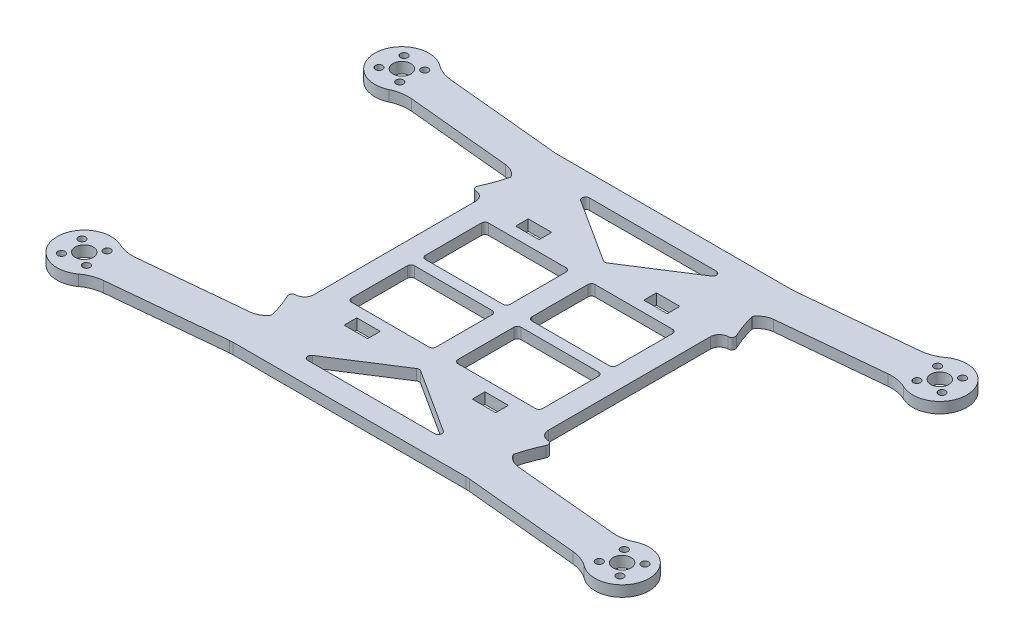
SolidWorks part; units mm, degrees
material "Custom PLA"
ref_plane "Front Plane" through (0, 0, 0) normal (0, 0, 1) x (1, 0, 0)
ref_plane "Top Plane" through (0, 0, 0) normal (0, 1, 0) x (1, 0, 0)
ref_plane "Right Plane" through (0, 0, 0) normal (1, 0, 0) x (0, 0, -1)
sketch "Sketch1" plane through (0, 0, 0) normal (0, 1, 0) x (1, 0, 0)
  line L0 (-101.3207, 0) -> (4964.7124, 0) construction
  line L1 (0, -101.3207) -> (0, 4964.7124) construction
  line L4 (33.2085, 45.046) -> (65.0466, 48.1117)
  line L5 (37.1258, 35.377) -> (66.0089, 38.1581)
  line L6 (0.5402, 25.8595) -> (18.1402, 37.1585)
  line L7 (4, 1.5) -> (25.5, 1.5)
  line L8 (3, 2.5) -> (3, 18)
  line L9 (4, 19) -> (25.5, 19)
  line L10 (26.5, 2.5) -> (26.5, 18)
  line L11 (14.5, 22) -> (21, 22)
  line L12 (14.5, 22) -> (14.5, 25.5)
  line L13 (14.5, 25.5) -> (21, 25.5)
  line L14 (21, 22) -> (21, 25.5)
  line L15 (17.6, 39) -> (-17.6, 39)
  line L16 (-18.1402, 37.1585) -> (-0.5402, 25.8595)
  line L17 (71.6376, 40.5277) -> (71.0277, 46.8624) construction
  line L18 (32.5, 22.4419) -> (32.5, -22.4419)
  line L30 (32.25, 45) -> (-32.25, 45)
  line L31 (-71.6376, 40.5277) -> (-71.0277, 46.8624) construction
  line L70 (-32.5, 22.4419) -> (-32.5, -22.4419)
  line L71 (-21, 22) -> (-21, 25.5)
  line L72 (-14.5, 25.5) -> (-21, 25.5)
  line L73 (-14.5, 22) -> (-14.5, 25.5)
  line L74 (-14.5, 22) -> (-21, 22)
  line L75 (-26.5, 2.5) -> (-26.5, 18)
  line L76 (-4, 19) -> (-25.5, 19)
  line L77 (-3, 2.5) -> (-3, 18)
  line L78 (-4, 1.5) -> (-25.5, 1.5)
  line L79 (-37.1258, 35.377) -> (-66.0089, 38.1581)
  line L80 (-33.2085, 45.046) -> (-65.0466, 48.1117)
  line L81 (-71.6376, -40.5277) -> (-71.0277, -46.8624) construction
  line L82 (71.6376, -40.5277) -> (71.0277, -46.8624) construction
  line L83 (-33.2085, -45.046) -> (-65.0466, -48.1117)
  line L84 (-37.1258, -35.377) -> (-66.0089, -38.1581)
  line L85 (-4, -1.5) -> (-25.5, -1.5)
  line L86 (-3, -2.5) -> (-3, -18)
  line L87 (-4, -19) -> (-25.5, -19)
  line L88 (-26.5, -2.5) -> (-26.5, -18)
  line L89 (-14.5, -22) -> (-21, -22)
  line L90 (-14.5, -22) -> (-14.5, -25.5)
  line L91 (-14.5, -25.5) -> (-21, -25.5)
  line L92 (-21, -22) -> (-21, -25.5)
  line L93 (32.25, -45) -> (-32.25, -45)
  line L94 (-18.1402, -37.1585) -> (-0.5402, -25.8595)
  line L95 (17.6, -39) -> (-17.6, -39)
  line L96 (21, -22) -> (21, -25.5)
  line L97 (14.5, -25.5) -> (21, -25.5)
  line L98 (14.5, -22) -> (14.5, -25.5)
  line L99 (14.5, -22) -> (21, -22)
  line L100 (26.5, -2.5) -> (26.5, -18)
  line L101 (4, -19) -> (25.5, -19)
  line L102 (3, -2.5) -> (3, -18)
  line L103 (4, -1.5) -> (25.5, -1.5)
  line L104 (0.5402, -25.8595) -> (18.1402, -37.1585)
  line L105 (37.1258, -35.377) -> (66.0089, -38.1581)
  line L106 (33.2085, -45.046) -> (65.0466, -48.1117)
  line L107 (67.0345, -43.2812) -> (81.9655, -44.7188) construction
  line L108 (73.7812, -51.4655) -> (75.2188, -36.5345) construction
  arc A3 (37.1258, 35.377) -> (33.4143, 33.1273) centre (37.605, 30.4) ccw
  arc A4 (71.2717, 37.2303) -> (66.0089, 38.1581) centre (66.9673, 28.2041) ccw
  arc A5 (65.0466, 48.1117) -> (70.0378, 50.0281) centre (64.0881, 58.0657) ccw
  arc A6 (71.2717, 37.2303) -> (70.0378, 50.0281) centre (74.5, 44) ccw
  arc A7 (-17.6, 39) -> (-18.1402, 37.1585) centre (-17.6, 38) ccw
  arc A8 (18.1402, 37.1585) -> (17.6, 39) centre (17.6, 38) ccw
  arc A9 (0.5402, 25.8595) -> (-0.5402, 25.8595) centre (0, 26.701) cw
  circle A10 centre (74.5, 44) radius 2.5
  circle A11 centre (71.0277, 46.8624) radius 1
  circle A12 centre (77.3624, 47.4723) radius 1
  circle A13 centre (77.9723, 41.1376) radius 1
  circle A14 centre (71.6376, 40.5277) radius 1
  arc A54 (32.25, 45) -> (33.2085, 45.046) centre (32.25, 55) ccw
  arc A98 (33.4143, 33.1273) -> (35.8354, 26.3563) centre (74.5, 44) ccw
  arc A99 (35.8354, 26.3563) -> (34.9469, 24.9414) centre (34.9257, 25.9411) cw
  arc A100 (34.9469, 24.9414) -> (32.5, 22.4419) centre (35, 22.4419) ccw
  arc A101 (-34.9469, 24.9414) -> (-32.5, 22.4419) centre (-35, 22.4419) cw
  arc A102 (-35.8354, 26.3563) -> (-34.9469, 24.9414) centre (-34.9257, 25.9411) ccw
  arc A103 (-33.4143, 33.1273) -> (-35.8354, 26.3563) centre (-74.5, 44) cw
  arc A104 (-32.25, 45) -> (-33.2085, 45.046) centre (-32.25, 55) cw
  circle A105 centre (-71.6376, 40.5277) radius 1
  circle A106 centre (-77.9723, 41.1376) radius 1
  circle A107 centre (-77.3624, 47.4723) radius 1
  circle A108 centre (-71.0277, 46.8624) radius 1
  circle A109 centre (-74.5, 44) radius 2.5
  arc A110 (-71.2717, 37.2303) -> (-70.0378, 50.0281) centre (-74.5, 44) cw
  arc A111 (-65.0466, 48.1117) -> (-70.0378, 50.0281) centre (-64.0881, 58.0657) cw
  arc A112 (-71.2717, 37.2303) -> (-66.0089, 38.1581) centre (-66.9673, 28.2041) cw
  arc A113 (-37.1258, 35.377) -> (-33.4143, 33.1273) centre (-37.605, 30.4) cw
  arc A114 (-37.1258, -35.377) -> (-33.4143, -33.1273) centre (-37.605, -30.4) ccw
  arc A115 (-71.2717, -37.2303) -> (-66.0089, -38.1581) centre (-66.9673, -28.2041) ccw
  arc A116 (-65.0466, -48.1117) -> (-70.0378, -50.0281) centre (-64.0881, -58.0657) ccw
  arc A117 (-71.2717, -37.2303) -> (-70.0378, -50.0281) centre (-74.5, -44) ccw
  circle A118 centre (-74.5, -44) radius 2.5
  circle A119 centre (-71.0277, -46.8624) radius 1
  circle A120 centre (-77.3624, -47.4723) radius 1
  circle A121 centre (-77.9723, -41.1376) radius 1
  circle A122 centre (-71.6376, -40.5277) radius 1
  arc A123 (-32.25, -45) -> (-33.2085, -45.046) centre (-32.25, -55) ccw
  arc A124 (-33.4143, -33.1273) -> (-35.8354, -26.3563) centre (-74.5, -44) ccw
  arc A125 (-35.8354, -26.3563) -> (-34.9469, -24.9414) centre (-34.9257, -25.9411) cw
  arc A126 (-34.9469, -24.9414) -> (-32.5, -22.4419) centre (-35, -22.4419) ccw
  arc A127 (34.9469, -24.9414) -> (32.5, -22.4419) centre (35, -22.4419) cw
  arc A128 (35.8354, -26.3563) -> (34.9469, -24.9414) centre (34.9257, -25.9411) ccw
  arc A129 (33.4143, -33.1273) -> (35.8354, -26.3563) centre (74.5, -44) cw
  arc A130 (32.25, -45) -> (33.2085, -45.046) centre (32.25, -55) cw
  circle A131 centre (71.6376, -40.5277) radius 1
  circle A132 centre (77.9723, -41.1376) radius 1
  circle A133 centre (77.3624, -47.4723) radius 1
  circle A134 centre (71.0277, -46.8624) radius 1
  circle A135 centre (74.5, -44) radius 2.5
  arc A136 (0.5402, -25.8595) -> (-0.5402, -25.8595) centre (0, -26.701) ccw
  arc A137 (18.1402, -37.1585) -> (17.6, -39) centre (17.6, -38) cw
  arc A138 (-17.6, -39) -> (-18.1402, -37.1585) centre (-17.6, -38) cw
  arc A139 (71.2717, -37.2303) -> (70.0378, -50.0281) centre (74.5, -44) cw
  arc A140 (65.0466, -48.1117) -> (70.0378, -50.0281) centre (64.0881, -58.0657) cw
  arc A141 (71.2717, -37.2303) -> (66.0089, -38.1581) centre (66.9673, -28.2041) cw
  arc A142 (37.1258, -35.377) -> (33.4143, -33.1273) centre (37.605, -30.4) cw
  arc A143 (25.5, 1.5) -> (26.5, 2.5) centre (25.5, 2.5) ccw
  arc A144 (25.5, 19) -> (26.5, 18) centre (25.5, 18) cw
  arc A145 (3, 18) -> (4, 19) centre (4, 18) cw
  arc A146 (4, 1.5) -> (3, 2.5) centre (4, 2.5) cw
  arc A147 (-3, 2.5) -> (-4, 1.5) centre (-4, 2.5) cw
  arc A148 (-4, 19) -> (-3, 18) centre (-4, 18) cw
  arc A149 (-26.5, 18) -> (-25.5, 19) centre (-25.5, 18) cw
  arc A150 (-26.5, 2.5) -> (-25.5, 1.5) centre (-25.5, 2.5) ccw
  arc A151 (3, -2.5) -> (4, -1.5) centre (4, -2.5) cw
  arc A152 (26.5, -2.5) -> (25.5, -1.5) centre (25.5, -2.5) ccw
  arc A153 (26.5, -18) -> (25.5, -19) centre (25.5, -18) cw
  arc A154 (4, -19) -> (3, -18) centre (4, -18) cw
  arc A155 (-25.5, -1.5) -> (-26.5, -2.5) centre (-25.5, -2.5) ccw
  arc A156 (-4, -1.5) -> (-3, -2.5) centre (-4, -2.5) cw
  arc A157 (-3, -18) -> (-4, -19) centre (-4, -18) cw
  arc A158 (-25.5, -19) -> (-26.5, -18) centre (-25.5, -18) cw
  point P37 (0, 25.5127)
  point P41 (77.9723, 41.1376)
  point P50 (74.5, 44)
  point P64 (32.5, 0)
  point P82 (0, 45)
  point P91 (-74.5, 44)
  point P164 (-32.5, 0)
  point P172 (-74.5, -44)
  point P173 (0, -45)
  point P174 (74.5, -44)
  point P175 (0, -25.5127)
  point P178 (26.5, 1.5)
  point P181 (26.5, 19)
  point P184 (3, 19)
  point P187 (3, 1.5)
  point P190 (-3, 1.5)
  point P193 (-3, 19)
  point P196 (-26.5, 19)
  point P199 (-26.5, 1.5)
  point P202 (3, -1.5)
  point P205 (26.5, -1.5)
  point P208 (26.5, -19)
  point P211 (3, -19)
  point P214 (-26.5, -1.5)
  point P217 (-3, -1.5)
  point P220 (-3, -19)
  point P223 (-26.5, -19)
  point P226 (77.9723, 41.1376)
  point P227 (77.9723, 41.1376)
  dimension "D5" = 42.5
  dimension "D6" = 5
  dimension "D7" = 10
  dimension "D8" = 7.5
  dimension "D9" = 149
  dimension "D10" = 88
  dimension "D16" = 14.5
  dimension "D18" = 1
  dimension "D30" = 5
  dimension "D11" = 10
  dimension "D22" = 6
  dimension "D33" = 1
  dimension "D29" = 2.5
  dimension "D34" = 1
  dimension "D35" = 2
  dimension "D4" = 174.5
  dimension "D12" = 32.5
  dimension "D13" = 10
  dimension "D14" = 64.5
  dimension "D15" = 6.5
  dimension "D17" = 3
  dimension "D19" = 35.2
  dimension "D20" = 32.7
  dimension "D21" = 23.5
  dimension "D23" = 6
  dimension "D24" = 1.5
  dimension "D25" = 45
  dimension "D26" = 30.4
  dimension "D27" = 3.5
  dimension "D28" = 22
  dimension "D31" = 4.5
  dimension "D32" = 4
extrude "Boss-Extrude1" add sketch "Sketch1" along normal mid plane 3
